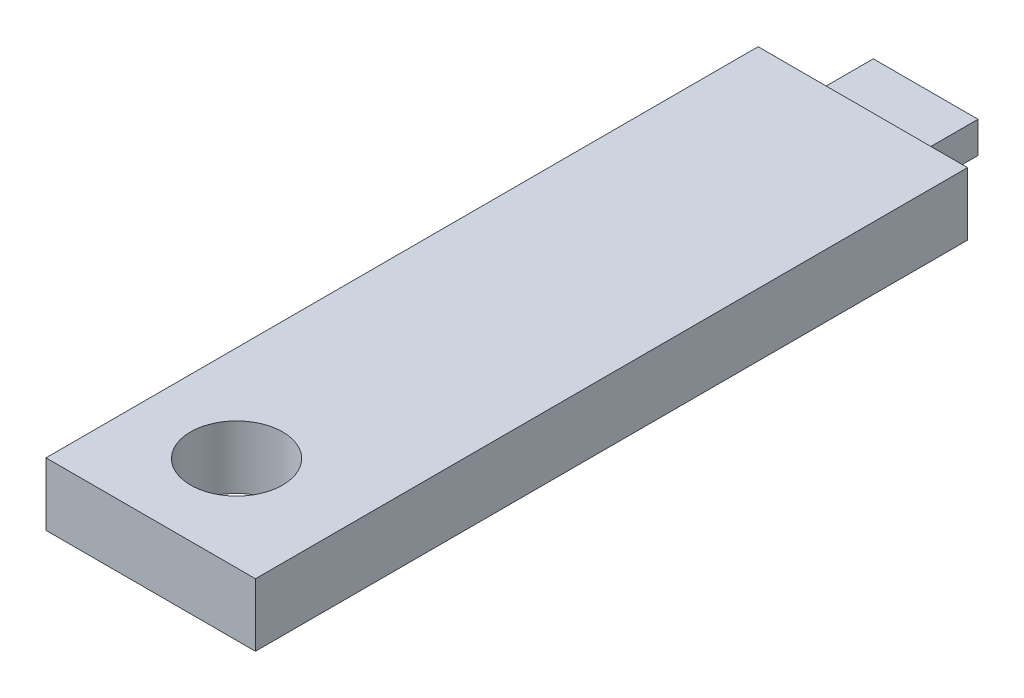
SolidWorks part; units mm, degrees
ref_plane "Front Plane" through (0, 0, 0) normal (0, 0, 1) x (1, 0, 0)
ref_plane "Top Plane" through (0, 0, 0) normal (0, 1, 0) x (1, 0, 0)
ref_plane "Right Plane" through (0, 0, 0) normal (1, 0, 0) x (0, 0, -1)
sketch "Sketch1" plane through (0, 0, 0) normal (0, 0, 1) x (1, 0, 0)
  line L1 (0, 0) -> (5, 0)
  line L2 (0, 0) -> (0, 1.5)
  line L3 (0, 1.5) -> (5, 1.5)
  line L4 (5, 0) -> (5, 1.5)
  dimension "D1" = 5
  dimension "D2" = 1.5
extrude "Boss-Extrude1" add sketch "Sketch1" along normal blind 3
sketch "Sketch2" plane through (0, 0, 3) normal (0, 0, 1) x (1, 0, 0)
  line L0 (0, 0) -> (5, 0) construction
  line L1 (-2.5, -0.75) -> (7.5, -0.75)
  line L2 (-2.5, -0.75) -> (-2.5, 2.25)
  line L3 (-2.5, 2.25) -> (7.5, 2.25)
  line L4 (7.5, -0.75) -> (7.5, 2.25)
  line L5 (0, 1.5) -> (0, 0) construction
  dimension "D1" = 10
  dimension "D2" = 3
  dimension "D3" = 0.75
  dimension "D4" = 2.5
extrude "Boss-Extrude2" add sketch "Sketch2" along normal blind 34
sketch "Sketch3" plane through (0, -0.75, 0) normal (0, -1, 0) x (1, 0, 0)
  circle A0 centre (2.0771, 32.478) radius 2.2
  dimension "D1" = 4.4
extrude "Cut-Extrude1" cut sketch "Sketch3" against normal through all
